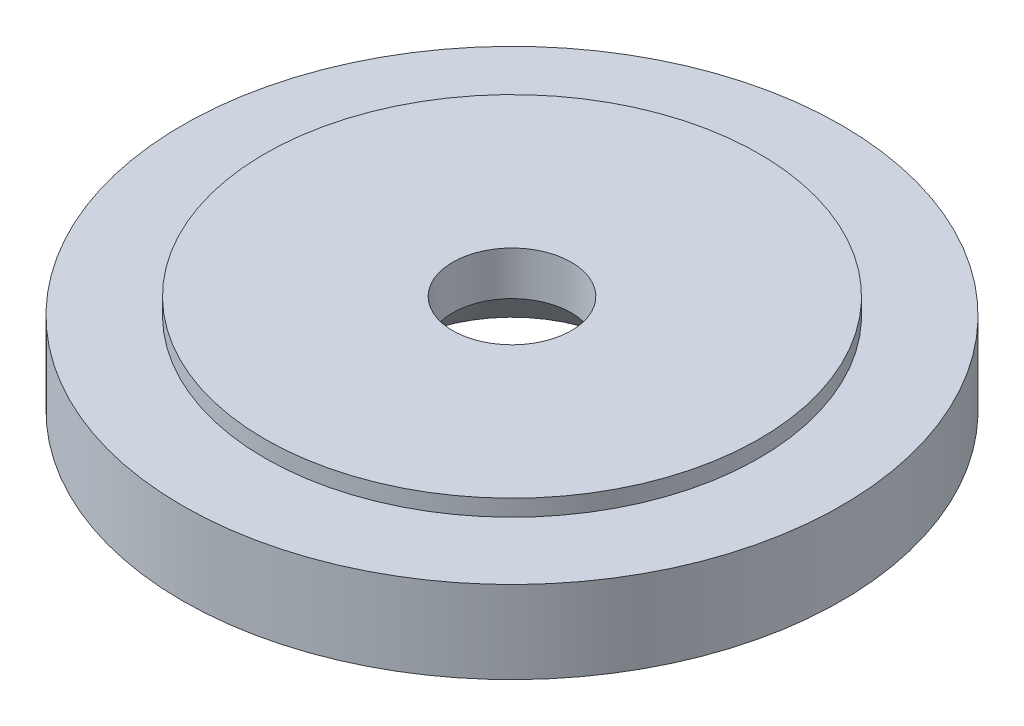
SolidWorks part; units mm, degrees
ref_plane "Front Plane" through (0, 0, 0) normal (0, 0, 1) x (1, 0, 0)
ref_plane "Top Plane" through (0, 0, 0) normal (0, 1, 0) x (1, 0, 0)
ref_plane "Right Plane" through (0, 0, 0) normal (1, 0, 0) x (0, 0, -1)
sketch "Sketch1" plane through (0, 0, 0) normal (0, 1, 0) x (1, 0, 0)
  circle A0 centre (0, 0) radius 10
  dimension "D1" = 20
extrude "Boss-Extrude1" add sketch "Sketch1" along normal blind 2.5
sketch "Sketch2" plane through (0, 2.5, 0) normal (0, 1, 0) x (1, 0, 0)
  circle A0 centre (0, 0) radius 7.5
  dimension "D1" = 15
extrude "Boss-Extrude2" add sketch "Sketch2" along normal blind 0.5
hole_wizard "CSK for M3 Hex Socket Countersunk Head Screw1" positions "Sketch3" profile "Sketch4" countersink size "M3" standard "DIN" end condition through all
sketch "Sketch3" plane through (0, 0, 0) normal (0, -1, 0) x (-1, 0, 0)
  point P0 (0, 0)
sketch "Sketch4" plane through (0, 0, 0) normal (1, 0, 0) x (0, 0, -1)
  line L0 (0, 0) -> (0, 3)
  line L1 (0, 3) -> (1.8, 3)
  line L2 (1.8, 3) -> (1.8, 1.67)
  line L3 (1.8, 1.67) -> (3.47, 0)
  line L5 (3.47, 0) -> (0, 0)
  line L6 (-1.8, 1.67) -> (-3.47, 0) construction
  line L11 (0, -6.35) -> (0, 107.95) construction
  dimension "Thru Hole Dia." = 3.6
  dimension "Thru Hole Depth" = 3
  dimension "Near C'Sink Dia." = 6.94
  dimension "Near C'Sink Angle" = 90
